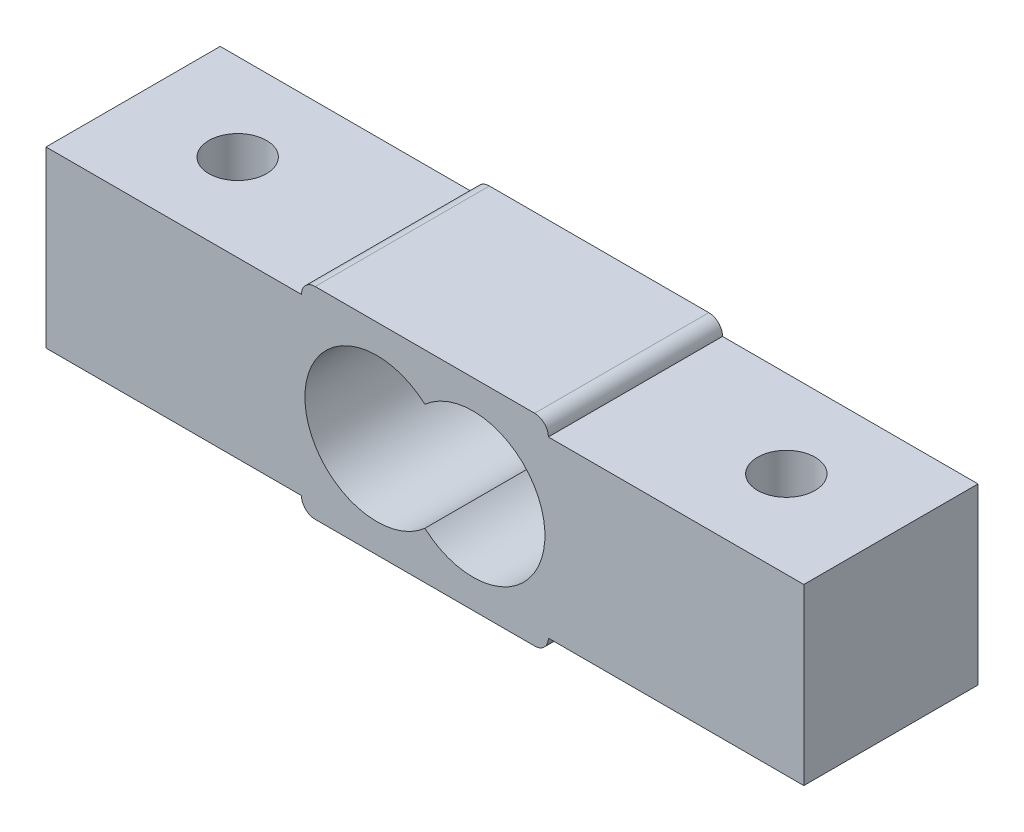
SolidWorks part; units mm, degrees
ref_plane "Front Plane" through (0, 0, 0) normal (0, 0, 1) x (1, 0, 0)
ref_plane "Top Plane" through (0, 0, 0) normal (0, 1, 0) x (1, 0, 0)
ref_plane "Right Plane" through (0, 0, 0) normal (1, 0, 0) x (0, 0, -1)
sketch "Sketch1" plane through (0, 0, 0) normal (0, 0, 1) x (1, 0, 0)
  line L1 (-27.625, -6.35) -> (27.625, -6.35)
  line L2 (-27.625, -6.35) -> (-27.625, 6.35)
  line L3 (-27.625, 6.35) -> (27.625, 6.35)
  line L4 (27.625, -6.35) -> (27.625, 6.35)
  line L5 (-27.625, -6.35) -> (27.625, 6.35) construction
  line L6 (-27.625, 6.35) -> (27.625, -6.35) construction
  point P0 (0, 0)
  dimension "D1" = 55.25
  dimension "D2" = 12.7
extrude "Boss-Extrude1" add sketch "Sketch1" along normal blind 12.7
sketch "Sketch2" plane through (0, 6.35, 0) normal (0, 1, 0) x (1, 0, 0)
  line L0 (-27.625, -6.35) -> (27.625, -6.35) construction
  line L1 (-27.625, -12.7) -> (-27.625, 0) construction
  line L2 (27.625, -12.7) -> (27.625, 0) construction
  point P6 (-20, -6.35)
  point P7 (20, -6.35)
  dimension "D1" = 7.625
  dimension "D2" = 7.625
hole_wizard "M5x0.8 Tapped Hole1" positions "3DSketch1" profile "Sketch3" tap size "M5x0.8" standard "ANSI Metric" end condition through all
sketch3d "3DSketch1"
  point P0 (-20, 6.35, 6.35)
  point P3 (20, 6.35, 6.35)
sketch "Sketch3" plane through (-20, 6.35, 6.35) normal (1, 0, 0) x (0, 0, 1)
  line L0 (0, 0) -> (0, 12.7)
  line L1 (0, 12.7) -> (2.1, 12.7)
  line L2 (2.1, 12.7) -> (2.1, 0)
  line L5 (2.1, 0) -> (0, 0)
  line L11 (0, -6.35) -> (0, 107.95) construction
  dimension "Thread Major Dia." = 4.2
  dimension "Thru Tap Drill Depth" = 12.7
sketch "Sketch4" plane through (0, 0, 12.7) normal (0, 0, 1) x (1, 0, 0)
  line L0 (0, 0) -> (-27.625, 0) construction
  line L1 (-27.625, 6.35) -> (-27.625, -6.35) construction
  line L2 (0, 0) -> (27.625, 0) construction
  line L3 (27.625, -6.35) -> (27.625, 6.35) construction
  arc A0 (0, 3.9131) -> (0, -3.9131) centre (-3.5, 0) ccw
  arc A1 (0, -3.9131) -> (0, 3.9131) centre (3.5, 0) ccw
  dimension "D1" = 10.5
  dimension "D2" = 10.5
  dimension "D3" = 3.5
  dimension "D4" = 3.5
extrude "Cut-Extrude1" cut sketch "Sketch4" against normal through all
sketch "Sketch5" plane through (0, 6.35, 0) normal (0, 1, 0) x (1, 0, 0)
  line L0 (0, 0) -> (0, -12.7) construction
  line L1 (27.625, 0) -> (-27.625, 0) construction
  line L2 (27.625, -12.7) -> (-27.625, -12.7) construction
  line L4 (-9, -12.7) -> (9, -12.7)
  line L5 (-9, -12.7) -> (-9, 0)
  line L6 (-9, 0) -> (9, 0)
  line L7 (9, -12.7) -> (9, 0)
  line L8 (-9, -12.7) -> (9, 0) construction
  line L9 (-9, 0) -> (9, -12.7) construction
  point P6 (0, -6.35)
  dimension "D1" = 18
extrude "Boss-Extrude2" add sketch "Sketch5" along normal blind 1
mirror "Mirror1" about plane through (0, 0, 0) normal (0, 1, 0) of "Boss-Extrude2"
fillet "Fillet1" radius 1 4 edges at (9, -7.35, 6.35) (-9, -7.35, 6.35) (-9, 7.35, 6.35) (9, 7.35, 6.35)
